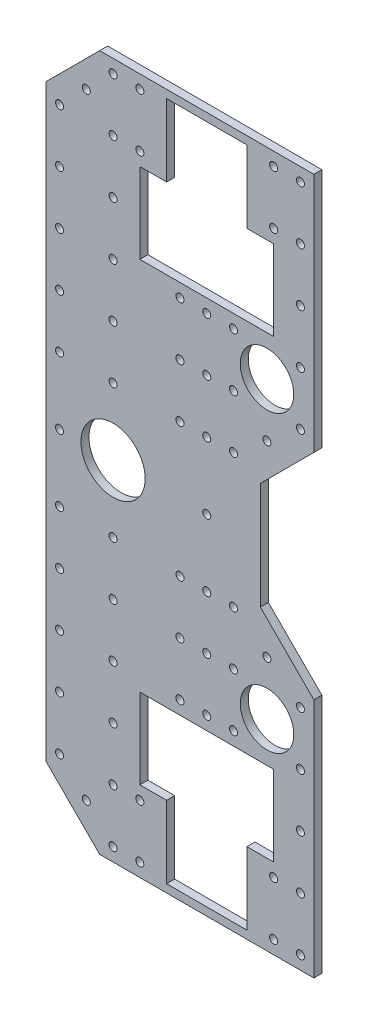
SolidWorks part; units mm, degrees
ref_plane "Front Plane" through (0, 0, 0) normal (0, 0, 1) x (1, 0, 0)
ref_plane "Top Plane" through (0, 0, 0) normal (0, 1, 0) x (1, 0, 0)
ref_plane "Right Plane" through (0, 0, 0) normal (1, 0, 0) x (0, 0, -1)
ref_axis "Axis2" through (0, 55.2999, 0) along (0, -1, 0)
ref_axis "Axis3" through (45, 0, 0) along (-1, 0, 0)
sketch "Sketch1" plane through (0, 0, 0) normal (0, 0, 1) x (1, 0, 0)
  line L0 (-60, 110) -> (-60, 0)
  line L1 (-60, 0) -> (20, 0)
  line L2 (-60, 110) -> (-40, 130)
  line L3 (-40, 130) -> (40, 130)
  line L5 (40, 130) -> (40, 40)
  line L6 (45, 0) -> (-65, 0) construction
  line L7 (40, 40) -> (20, 20)
  line L8 (0, 55.2999) -> (0, -60.0643) construction
  line L9 (-25, 100) -> (-15, 100)
  line L10 (-15, 100) -> (-15, 127)
  line L11 (-25, 100) -> (-25, 70)
  line L12 (-25, 70) -> (25, 70)
  line L13 (25, 100) -> (25, 70)
  line L14 (-15, 127) -> (15, 127)
  line L15 (15, 127) -> (15, 100)
  line L16 (15, 100) -> (25, 100)
  line L17 (20, 20) -> (20, 0)
  point P23 (0, 70)
  dimension "D3" = 20
  dimension "D4" = 25
  dimension "D1" = 110
  dimension "D2" = 130
  dimension "D5" = 28.2843
  dimension "D6" = 60
  dimension "D7" = 20
  dimension "D8" = 80
  dimension "D9" = 20
  dimension "D10" = 90
  dimension "D11" = 3
  dimension "D15" = 25
  dimension "D22" = 30
  dimension "D23" = 70
  dimension "D24" = 27
  dimension "D25" = 30
extrude "Main" add sketch "Sketch1" along normal blind 3
sketch "Sketch2" plane through (0, 0, 3) normal (0, 0, 1) x (1, 0, 0)
  line L0 (45, 0) -> (-65, 0) construction
  line L1 (-60, 110) -> (-60, 0) construction
  line L2 (0, 55.2999) -> (0, -60.0643) construction
  line L3 (-60, 0) -> (20, 0) construction
  line L4 (-60, 110) -> (-60, 0) construction
  circle A0 centre (-35, 0) radius 12
  circle A1 centre (-55, 0) radius 1.5
  circle A2 centre (22.5, 55) radius 10
  circle A3 centre (0, 0) radius 1.5
  circle A4 centre (-45, 115) radius 1.5
  circle A5 centre (22.5, 35) radius 1.5
  dimension "D1" = 24
  dimension "D3" = 3
  dimension "D5" = 22.5
  dimension "D7" = 20
  dimension "D8" = 3
  dimension "D11" = 35
  dimension "D12" = 3
  dimension "D2" = 25
  dimension "D4" = 5
  dimension "D6" = 55
  dimension "D9" = 15
  dimension "D10" = 5
extrude "SingleHoles" cut sketch "Sketch2" against normal through all
sketch "Sketch3" plane through (0, 0, 3) normal (0, 0, 1) x (1, 0, 0)
  circle A0 centre (-35, 125) radius 1.5
  dimension "D1" = 3
  dimension "D2" = 5
  dimension "D3" = 5
extrude "TopLeftHole" cut sketch "Sketch3" against normal through all
pattern_linear "TopLeft2HoleLinearPattern" count 6 spacing 20 along (0, -1, 0) of "TopLeftHole"
sketch "Sketch4" plane through (0, 0, 3) normal (0, 0, 1) x (1, 0, 0)
  line L0 (-60, 110) -> (-60, 0) construction
  circle A0 centre (-35, 105) radius 1.5
  circle A3 centre (-55, 105) radius 1.5
  dimension "D1" = 3
  dimension "D2" = 5
  dimension "D3" = 20
  dimension "D4" = 5
extrude "TopLeft1Hole" cut sketch "Sketch4" against normal through all
pattern_linear "TopLeft1HoleLinearPattern" count 5 spacing 20 along (0, -1, 0) of "TopLeft1Hole"
sketch "Sketch5" plane through (0, 0, 3) normal (0, 0, 1) x (1, 0, 0)
  line L1 (-40, 130) -> (40, 130) construction
  circle A0 centre (35, 125) radius 1.5
  dimension "D1" = 3
  dimension "D2" = 5
  dimension "D3" = 5
extrude "TopRightHole" cut sketch "Sketch5" against normal through all
pattern_linear "TopRightHoleLinearPattern" count 5 spacing 20 along (0, -1, 0) of "TopRightHole"
sketch "MotorHoleFixSketch" plane through (0, 0, 3) normal (0, 0, 1) x (1, 0, 0)
  line L0 (0, 55.2999) -> (0, -60.0643) construction
  line L1 (-60, 0) -> (20, 0) construction
  circle A0 centre (0, 65) radius 1.5
  circle A1 centre (-10, 65) radius 1.5
  circle A2 centre (10, 65) radius 1.5
  dimension "D1" = 3
  dimension "D2" = 65
  dimension "D3" = 10
  dimension "D4" = 10
extrude "MotorHoleFix" cut sketch "MotorHoleFixSketch" against normal through all
pattern_linear "MotorHoleFixLinearPattern" count 3 spacing 20 along (0, -1, 0) of "MotorHoleFix"
sketch "Sketch6" plane through (0, 0, 3) normal (0, 0, 1) x (1, 0, 0)
  line L0 (-40, 130) -> (40, 130) construction
  circle A0 centre (25, 125) radius 1.5
  circle A2 centre (25, 105) radius 1.5
  circle A3 centre (35, 125) radius 1.5 construction
  dimension "D1" = 3
  dimension "D2" = 20
  dimension "D4" = 10
  dimension "D5" = 5
extrude "Cut-Extrude1" cut sketch "Sketch6" against normal through all
mirror "Mirror1" about plane through (0, 0, 0) normal (1, 0, 0) of "Cut-Extrude1"
mirror "LeftRightMirror" about plane through (0, 0, 0) normal (0, 1, 0) of bodies 113 101
